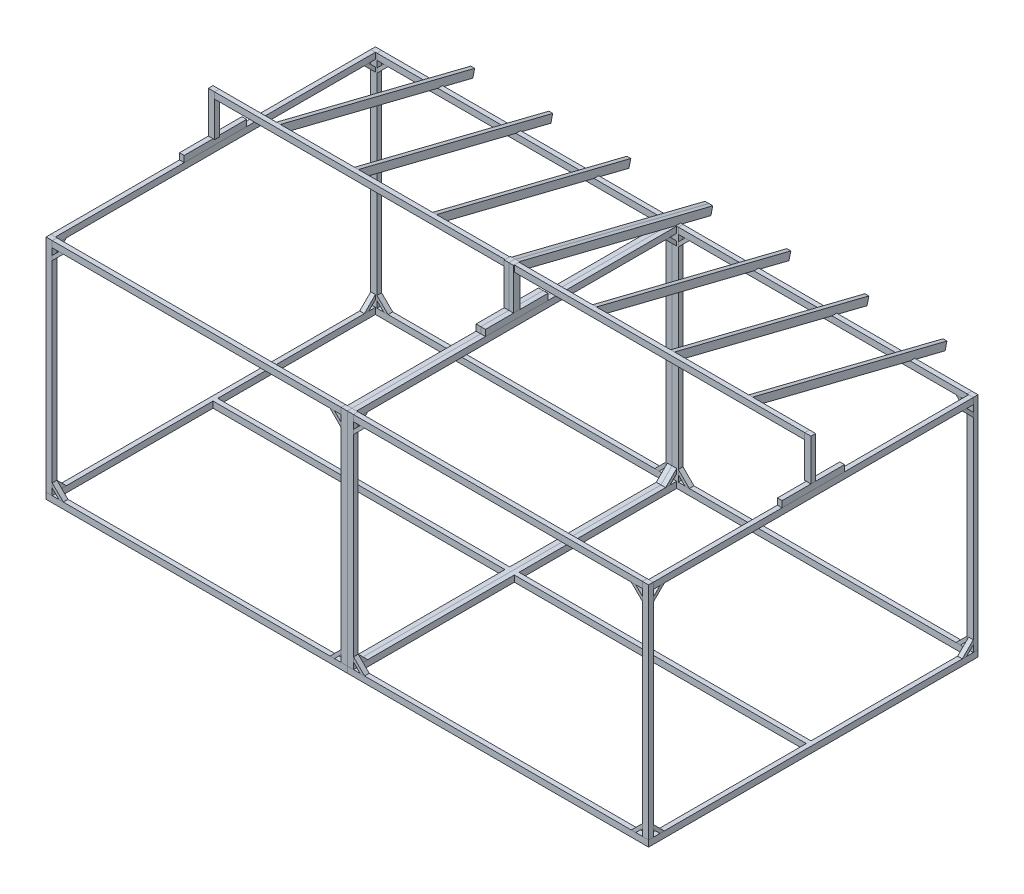
SolidWorks part; units mm, degrees
other "DetailItem8"
other "DetailItem9"
other "DetailItem10"
other "DetailItem11"
other "DetailItem12"
other "DetailItem13"
other "DetailItem14"
other "DetailItem15"
other "DetailItem16"
other "DetailItem17"
ref_plane "Front Plane" through (0, 0, 0) normal (0, 0, 1) x (1, 0, 0)
ref_plane "Top Plane" through (0, 0, 0) normal (0, 1, 0) x (1, 0, 0)
ref_plane "Right Plane" through (0, 0, 0) normal (1, 0, 0) x (0, 0, -1)
other "Configuration Table"
sketch "MetalBase" plane through (0, 0, 0) normal (0, 1, 0) x (1, 0, 0)
  line L0 (-60, -60) -> (7660, -60)
  line L1 (0, 0) -> (7600, 0)
  line L2 (0, 0) -> (0, 2020)
  line L3 (0, 4100) -> (7600, 4100)
  line L4 (7600, 0) -> (7600, 2020)
  line L5 (7660, -60) -> (7660, 4160)
  line L6 (-60, 4160) -> (7660, 4160)
  line L7 (-60, -60) -> (-60, 4160)
  line L8 (0, 2050) -> (7600, 2050) construction
  line L9 (0, 2020) -> (7600, 2020)
  line L10 (0, 2080) -> (7600, 2080)
  line L11 (0, 2080) -> (0, 4100)
  line L12 (7600, 2080) -> (7600, 4100)
  line L13 (0, 0) -> (0, 4100) construction
  line L15 (7600, 0) -> (7600, 4100) construction
  point P15 (7660, 2050)
  dimension "D1" = 4100
  dimension "D2" = 7600
  dimension "D6" = 4220
  dimension "D7" = 7720
  dimension "D3" = 60
  dimension "D4" = 30
  dimension "D5" = 30
sketch "InternalSpace" plane through (0, 0, 0) normal (0, 1, 0) x (1, 0, 0)
  line L26 (50, 50) -> (7550, 50)
  line L27 (7550, 50) -> (7550, 4050)
  line L28 (7550, 4050) -> (50, 4050)
  line L29 (50, 4050) -> (50, 50)
  line L30 (50, 50) -> (7550, 50)
  line L31 (7550, 50) -> (7550, 4050)
  line L32 (7550, 4050) -> (50, 4050)
  line L33 (50, 4050) -> (50, 50)
  dimension "D2" = 4000
  dimension "D3" = 7500
  dimension "D1" = 110
sketch "Furniture" [suppressed] plane through (0, 0, 0) normal (0, 1, 0) x (1, 0, 0)
  line L0 (6750, 2050) -> (6750, 4050)
  line L1 (2200, 2550) -> (1400, 2550)
  line L2 (2200, 2550) -> (2200, 4050)
  line L3 (2200, 4050) -> (1400, 4050)
  line L4 (1400, 2550) -> (1400, 4050)
  line L5 (1050, 50) -> (50, 50)
  line L6 (1050, 50) -> (1050, 2050)
  line L7 (1050, 2050) -> (50, 2050)
  line L8 (50, 50) -> (50, 2050)
  line L9 (6350, 2110) -> (7550, 2110)
  line L10 (2200, 4050) -> (2200, 150)
  line L11 (0, 0) -> (7600, 0) construction
  line L12 (6350, 50) -> (6350, 2110)
  line L13 (6470, 50) -> (6470, 1990)
  line L15 (2200, 2050) -> (7550, 2050) construction
  line L17 (1979.5569, 919.0285) -> (2200, 150)
  line L18 (6350, 150) -> (5722.0427, 459.305)
  line L19 (6710, 1120.0467) -> (7310, 1120.0467)
  line L24 (6710, 1120.0467) -> (6710, 1880.0467)
  line L25 (6710, 1880.0467) -> (7310, 1880.0467)
  line L26 (7310, 1120.0467) -> (7310, 1880.0467)
  line L27 (6350, 2110) -> (5750, 2110)
  line L28 (6350, 2110) -> (6350, 1510)
  line L29 (6350, 1510) -> (5750, 1510)
  line L30 (5750, 2110) -> (5750, 1510)
  line L31 (2320, 2050) -> (4320, 2050) construction
  line L32 (4320, 2050) -> (4320, 4050) construction
  line L33 (2200, 150) -> (2499.3532, 150) construction
  line L34 (2499.3532, 150) -> (2499.3532, 981.1813) construction
  line L35 (2499.3532, 981.1813) -> (2200, 981.1813) construction
  line L36 (2320, 4050) -> (2320, 150)
  line L37 (2200, 150) -> (2200, 50)
  line L38 (50, 50) -> (7550, 50) construction
  line L39 (2320, 150) -> (2320, 50)
  line L40 (7550, 4050) -> (50, 4050) construction
  line L41 (7550, 50) -> (7550, 4050) construction
  line L42 (50, 4050) -> (50, 50) construction
  line L43 (7550, 4050) -> (50, 4050) construction
  line L44 (7550, 50) -> (7550, 4050) construction
  line L45 (50, 50) -> (7550, 50) construction
  line L46 (50, 4050) -> (50, 50) construction
  line L47 (7010, 1120.0467) -> (7010, 1445.9123) construction
  line L48 (6470, 1990) -> (7550, 1990)
  line L49 (-60, -60) -> (-60, 4160) construction
  line L50 (7550, 809.8905) -> (7383.7397, 809.8905)
  line L51 (7550, 809.8905) -> (7550, 230.8186)
  line L52 (7550, 230.8186) -> (7383.7397, 230.8186)
  line L53 (7283.7397, 709.8905) -> (7283.7397, 330.8186)
  line L54 (7660, 4160) -> (-60, 4160) construction
  line L55 (-60, 4160) -> (-60, -60) construction
  line L56 (-60, -60) -> (7660, -60) construction
  line L57 (7660, -60) -> (7660, 4160) construction
  arc A1 (1979.5569, 919.0285) -> (1414.1883, 0) centre (2200, 150) ccw construction
  arc A2 (5722.0427, 459.305) -> (6350, 850) centre (6350, 150) cw construction
  arc A3 (7383.7397, 230.8186) -> (7283.7397, 330.8186) centre (7383.7397, 330.8186) cw
  arc A4 (7383.7397, 809.8905) -> (7283.7397, 709.8905) centre (7383.7397, 709.8905) ccw
  point P56 (7010, 1990)
  dimension "D13" = 600
  dimension "D21" = 100
  dimension "D1" = 1500
  dimension "D2" = 800
  dimension "D3" = 2000
  dimension "D4" = 1000
  dimension "D5" = 100
  dimension "D6" = 60
  dimension "D7" = 700
  dimension "D8" = 600
  dimension "D9" = 2260
  dimension "D10" = 800
  dimension "D11" = 100
  dimension "D12" = 760
  dimension "D14" = 2000
  dimension "D15" = 800
  dimension "D16" = 2000
  dimension "D17" = 600
  dimension "D18" = 60
  dimension "D19" = 4150
  dimension "D20" = 120
  dimension "D22" = 120
  dimension "D23" = 110
  dimension "D25" = 4220
  dimension "D26" = 1200
  dimension "D27" = 4030
  dimension "D24" = 110
sketch "Metal frame" plane through (0, 0, 0) normal (0, 1, 0) x (1, 0, 0)
  line L0 (0, 4100) -> (7600, 4100) construction
  line L1 (0, 4100) -> (7600, 4100)
  line L3 (0, 0) -> (0, 2020)
  line L4 (0, 0) -> (7600, 0) construction
  line L5 (0, 0) -> (7600, 0)
  line L7 (7600, 0) -> (7600, 2020)
  line L8 (-60, 4160) -> (7660, 4160)
  line L9 (7660, -60) -> (7660, 4160)
  line L10 (-60, -60) -> (7660, -60)
  line L11 (-60, -60) -> (-60, 4160)
  line L12 (0, 2050) -> (62.1159, 2050) construction
  line L13 (7600, 2080) -> (0, 2080)
  line L15 (7600, 2020) -> (0, 2020)
  line L17 (7600, 2080) -> (7600, 4100)
  line L18 (0, 2080) -> (0, 4100)
  line L19 (7600, 0) -> (7600, 4100) construction
  line L21 (0, 0) -> (0, 4100) construction
  point P14 (-60, 2050)
  dimension "D2" = 7720
  dimension "D3" = 4220
  dimension "D4" = 60
  dimension "D1" = 60
sketch "Walls bottom" plane through (0, 0, 0) normal (0, 1, 0) x (1, 0, 0)
  line L0 (-60, 4160) -> (7660, 4160) construction
  line L2 (-60, -60) -> (7660, -60) construction
  line L3 (7660, -60) -> (7660, 4160) construction
  line L4 (-60, -60) -> (-60, 4160) construction
  line L5 (-60, -60) -> (7660, -60)
  line L6 (7660, -60) -> (7660, 4160)
  line L7 (-60, 4160) -> (7660, 4160)
  line L8 (-60, -60) -> (-60, 4160)
  line L9 (40, 40) -> (40, 4060)
  line L10 (40, 4060) -> (7560, 4060)
  line L11 (7560, 40) -> (7560, 4060)
  line L12 (40, 40) -> (7560, 40)
  dimension "D2" = 4020
  dimension "D3" = 7520
  dimension "D4" = 7720
  dimension "D5" = 4220
  dimension "D1" = 100
sketch "Sketch15" [suppressed] plane through (0, 0, 0) normal (0, 1, 0) x (1, 0, 0)
  line L2 (7550, 50) -> (5502.4266, 50)
  line L3 (7550, 50) -> (7550, 1250)
  line L4 (7550, 1250) -> (5502.4266, 1250)
  line L5 (5502.4266, 50) -> (5502.4266, 1250)
  dimension "D1" = 1200
extrude "MetalFrame" add sketch "Metal frame" against normal blind 80 contours L11 L10 L9 L8 L15 L7 L5 L3 L13 L18 L1 L17 region at (3800, 0, -2050)
sketch "Sketch18" plane through (0, 0, 0) normal (0, 1, 0) x (1, 0, 0)
  line L0 (0, 0) -> (7600, 0) construction
  line L1 (3800, -1014.8769) -> (8467.9433, -1014.8769)
  line L2 (3800, -1014.8769) -> (3800, 5493.3133)
  line L3 (3800, 5493.3133) -> (8467.9433, 5493.3133)
  line L4 (8467.9433, -1014.8769) -> (8467.9433, 5493.3133)
  point P6 (3800, 0)
extrude "Cut-Extrude1" cut sketch "Sketch18" against normal through all
sketch "Sketch19" plane through (0, 0, 0) normal (0, 1, 0) x (1, 0, 0)
  line L0 (0, 0) -> (3800, 0) construction
  line L1 (3800, 4100) -> (3740, 4100)
  line L2 (3800, 4100) -> (3800, 0)
  line L3 (3800, 0) -> (3740, 0)
  line L4 (3740, 4100) -> (3740, 0)
  dimension "D1" = 60
extrude "Boss-Extrude1" add sketch "Sketch19" against normal blind 80
sketch "Roof" plane through (0, 0, 0) normal (1, 0, 0) x (0, 0, -1)
  line L0 (2050, 0) -> (2050, 3357.5) construction
  line L1 (4160, 0) -> (-60, 0) construction
  line L2 (4160, 0) -> (4160, 2830) construction
  line L3 (4160, 2830) -> (2050, 3357.5) construction
  line L4 (2050, 3357.5) -> (5424.8088, 3357.5) construction
  line L5 (4160, 2830) -> (4548.057, 2732.9857) construction
  line L6 (4160, 150) -> (-211.81, 150) construction
  line L7 (4160, 2830) -> (2960, 2830)
  line L8 (2960, 2830) -> (2960, 3130)
  line L9 (4160, 2750) -> (2401.0379, 2750) construction
  dimension "D2" = 1200
  dimension "D3" = 150
  dimension "D4" = 2174.9382
  dimension "D5" = 400
  dimension "D6" = 2574.9382
  dimension "D7" = 2830
  dimension "D8" = 300
  dimension "D9" = 3207.5
  dimension "D10" = 14.036
  dimension "D11" = 80
  dimension "D12" = 2600
sketch "Sketch23" plane through (-60, 0, 0) normal (1, 0, 0) x (0, 0, -1)
  line L0 (2050, 0) -> (2050, 3357.5) construction
  line L1 (4160, 0) -> (4100, 0)
  line L2 (4160, 0) -> (4160, 2830)
  line L3 (4160, 2830) -> (4100, 2830)
  line L4 (4100, 0) -> (4100, 2830)
  line L5 (0, 0) -> (0, 2830)
  line L6 (-60, 2830) -> (0, 2830)
  line L7 (-60, 0) -> (-60, 2830)
  line L8 (-60, 0) -> (0, 0)
  line L10 (0, 2830) -> (4100, 2830)
  line L11 (0, 2830) -> (0, 2750)
  line L12 (0, 2750) -> (4100, 2750)
  line L13 (4100, 2830) -> (4100, 2750)
  line M8 (-60, 0) -> (4160, 0)
  dimension "D1" = 60
  dimension "D2" = 80
extrude "Boss-Extrude5" add sketch "Sketch23" along normal blind 80 separate body contours L4 L3 L2 M8 | L7 L6 L5 M8 region at (-60, 1415, -4130) region at (-60, 1415, 30)
extrude "Boss-Extrude6" add sketch "Sketch23<3>" along normal blind 60 separate body contours L0 L12 L5 L10 | L12 L0 L10 L4 region at (-60, 2790, -1025) region at (-60, 2790, -3075)
sketch "Sketch23<3>" plane through (-60, 0, 0) normal (1, 0, 0) x (0, 0, -1) same geometry as "Sketch23"
extrude "Boss-Extrude7" add sketch "Sketch23<5>" against normal blind 80 from surface separate body contours L4 L3 L2 M8 | L7 L6 L5 M8 region at (-60, 1415, -4130) region at (-60, 1415, 30) starting at face at (3800, -40, -2050)
sketch "Sketch23<5>" plane through (-60, 0, 0) normal (1, 0, 0) x (0, 0, -1) same geometry as "Sketch23"
extrude "Boss-Extrude8" add sketch "Sketch23<6>" against normal blind 60 from surface separate body contours L12 L0 L10 L4 | L0 L12 L5 L10 region at (-60, 2790, -1025) region at (-60, 2790, -3075) starting at face at (3800, 1415, 30)
sketch "Sketch23<6>" plane through (-60, 0, 0) normal (1, 0, 0) x (0, 0, -1) same geometry as "Sketch23"
sketch "Sketch24" plane through (0, 2830, 0) normal (0, 1, 0) x (1, 0, 0)
  line L1 (20, 4160) -> (3720, 4160)
  line L2 (20, 4160) -> (20, 4100)
  line L3 (20, 4100) -> (3720, 4100)
  line L4 (3720, 4160) -> (3720, 4100)
  line L5 (20, 0) -> (3720, 0)
  line L6 (20, 0) -> (20, -60)
  line L7 (20, -60) -> (3720, -60)
  line L8 (3720, 0) -> (3720, -60)
extrude "Boss-Extrude9" add sketch "Sketch24" against normal blind 80 separate body
sketch "Sketch25" plane through (3800, 0, 0) normal (1, 0, 0) x (0, 0, -1)
  line L5 (2020, 2910) -> (2080, 2910)
  line L6 (2020, 2910) -> (2020, 3440)
  line L7 (2020, 3440) -> (2080, 3440)
  line L8 (2080, 2910) -> (2080, 3440)
  line L9 (2050, 0) -> (2050, 3357.5) construction
  line L10 (0, 2830) -> (4100, 2830) construction
  line L12 (1650, 2830) -> (2450, 2830)
  line L13 (1650, 2830) -> (1650, 2910)
  line L14 (1650, 2910) -> (2450, 2910)
  line L15 (2450, 2830) -> (2450, 2910)
  point P7 (2050, 3440)
  point P11 (2050, 2910)
  line M8 (4100, 2830) -> (0, 2830)
  dimension "D1" = 530
  dimension "D2" = 60
  dimension "D4" = 800
  dimension "D5" = 80
extrude "Boss-Extrude10" add sketch "Sketch25" along normal blind 80 from surface separate body contours L5 L8 L7 L6 region at (3800, 3175, -2050) starting at face at (-60, 2790, -2050)
extrude "Boss-Extrude13" add sketch "Sketch25<4>" against normal blind 60 from surface separate body contours L15 L14 L5 L13 M8 region at (3800, 2870, -2050) starting at face at (0, 2790, -2050)
sketch "Sketch25<4>" plane through (3800, 0, 0) normal (1, 0, 0) x (0, 0, -1) same geometry as "Sketch25"
extrude "Boss-Extrude20" add sketch "Sketch25<5>" against normal blind 60 separate body contours L15 L14 L5 L13 M8 region at (3800, 2870, -2050)
sketch "Sketch25<5>" plane through (3800, 0, 0) normal (1, 0, 0) x (0, 0, -1) same geometry as "Sketch25"
sketch "Sketch33" plane through (0, 2910, 0) normal (0, 1, 0) x (1, 0, 0)
  line L0 (3740, 1650) -> (3740, 2450) construction
  line L1 (3740, 2090) -> (3800, 2090)
  line L2 (3740, 2090) -> (3740, 2010)
  line L3 (3740, 2010) -> (3800, 2010)
  line L4 (3800, 2090) -> (3800, 2010)
  line L5 (3800, 1650) -> (3800, 2450) construction
  point P8 (3740, 2050)
  point P9 (3740, 2050)
  dimension "D1" = 80
extrude "Boss-Extrude21" add sketch "Sketch33" along normal up to surface (530 mm away) separate body up to face at (-20, 3440, -2050)
sketch "Sketch26" plane through (3800, 0, 0) normal (1, 0, 0) x (0, 0, -1)
  line L0 (4548.057, 2717.9857) -> (4160, 2815)
  line L1 (4548.057, 2717.9857) -> (4572.3106, 2815)
  line L3 (4572.3106, 2815) -> (2080, 3438.0776)
  line L4 (4100, 2815) -> (4100, 2830) construction
  line L5 (4100, 2830) -> (4160, 2830)
  line L6 (4160, 2830) -> (4160, 2815)
  line L7 (2080, 3335) -> (2080, 3438.0776)
  line L8 (4100, 2830) -> (2080, 3335)
  dimension "D1" = 100
extrude "Boss-Extrude12" add sketch "Sketch26" against normal blind 50 separate body
pattern_linear "LPattern1" count 4 spacing 1000 along (-1, 0, 0) of bodies 346
ref_plane "Plane1" through (1870, 0, 0) normal (-1, 0, 0) x (0, 0, 1)
sketch "Sketch27" plane through (3740, 0, 0) normal (-1, 0, 0) x (0, 0, 1)
  line L0 (-2020, 2910) -> (-2020, 3440) construction
  line L1 (-2080, 3440) -> (-2020, 3440)
  line L2 (-2080, 3440) -> (-2080, 3360)
  line L3 (-2080, 3360) -> (-2020, 3360)
  line L4 (-2020, 3440) -> (-2020, 3360)
  line L5 (-2050, 0) -> (-2050, 3357.5) construction
  point P4 (-2050, 3440)
  dimension "D1" = 80
  dimension "D2" = 60
extrude "Boss-Extrude22" add sketch "Sketch27" along normal up to surface (3720 mm away) separate body up to face at (20, 3175, -2050)
mirror "Mirror2" about plane through (3800, -80, 1014.8769) normal (-1, 0, 0) of bodies 336 338 340 342 335 337 339 341 330 412 411 349 348 347 346 410 350 351 354 352 353
sketch "Sketch28" plane through (0, 0, 60) normal (0, 0, 1) x (1, 0, 0)
  line L0 (20, 2665.1472) -> (104.8528, 2750)
  line L1 (20, 2750) -> (3720, 2750) construction
  line L2 (20, 0) -> (20, 2830) construction
  line L3 (20, 2608.5786) -> (161.4214, 2750)
  line L4 (20, 2665.1472) -> (20, 2750) construction
  line L5 (20, 2750) -> (104.8528, 2750) construction
  line L6 (3720, 2750) -> (20, 0) construction
  line L7 (20, 2750) -> (3720, 0) construction
  line L8 (104.8528, 2750) -> (161.4214, 2750)
  line L9 (20, 2665.1472) -> (20, 2608.5786)
  line L10 (1870, 1375) -> (1870, 2476.0047) construction
  line L11 (1870, 1375) -> (689.8346, 1375) construction
  line L12 (20, 0) -> (104.8528, 0) construction
  line L13 (20, 84.8528) -> (20, 0) construction
  line L14 (20, 84.8528) -> (20, 141.4214)
  line L15 (104.8528, 0) -> (161.4214, 0)
  line L16 (20, 141.4214) -> (161.4214, 0)
  line L17 (20, 84.8528) -> (104.8528, 0)
  line L18 (3720, 84.8528) -> (3720, 0) construction
  line L19 (3720, 0) -> (3635.1472, 0) construction
  line L20 (3720, 2750) -> (3635.1472, 2750) construction
  line L21 (3720, 2665.1472) -> (3720, 2750) construction
  line L22 (3720, 84.8528) -> (3635.1472, 0)
  line L23 (3720, 141.4214) -> (3578.5786, 0)
  line L24 (3635.1472, 0) -> (3578.5786, 0)
  line L25 (3720, 84.8528) -> (3720, 141.4214)
  line L26 (3720, 2665.1472) -> (3720, 2608.5786)
  line L27 (3635.1472, 2750) -> (3578.5786, 2750)
  line L28 (3720, 2608.5786) -> (3578.5786, 2750)
  line L29 (3720, 2665.1472) -> (3635.1472, 2750)
  line L30 (3800, -80) -> (3800, -237.922) construction
  line L31 (3880, 2665.1472) -> (3880, 2750) construction
  line L32 (3880, 2750) -> (3964.8528, 2750) construction
  line L33 (3880, 0) -> (3964.8528, 0) construction
  line L34 (3880, 84.8528) -> (3880, 0) construction
  line L35 (7580, 84.8528) -> (7580, 0) construction
  line L36 (7580, 0) -> (7495.1472, 0) construction
  line L37 (5730, 1375) -> (6910.1654, 1375) construction
  line L38 (5730, 1375) -> (5730, 2476.0047) construction
  line L39 (7580, 2750) -> (3880, 0) construction
  line L40 (3880, 2750) -> (7580, 0) construction
  line L41 (7580, 2750) -> (7495.1472, 2750) construction
  line L42 (7580, 2665.1472) -> (7580, 2750) construction
  line L43 (3880, 2665.1472) -> (3964.8528, 2750)
  line L44 (3880, 2608.5786) -> (4021.4214, 2750)
  line L45 (3964.8528, 2750) -> (4021.4214, 2750)
  line L46 (3880, 2665.1472) -> (3880, 2608.5786)
  line L47 (3880, 84.8528) -> (3880, 141.4214)
  line L48 (3964.8528, 0) -> (4021.4214, 0)
  line L49 (3880, 141.4214) -> (4021.4214, 0)
  line L50 (3880, 84.8528) -> (3964.8528, 0)
  line L51 (7580, 84.8528) -> (7495.1472, 0)
  line L52 (7580, 141.4214) -> (7438.5786, 0)
  line L53 (7495.1472, 0) -> (7438.5786, 0)
  line L54 (7580, 84.8528) -> (7580, 141.4214)
  line L55 (7580, 2665.1472) -> (7580, 2608.5786)
  line L56 (7495.1472, 2750) -> (7438.5786, 2750)
  line L57 (7580, 2608.5786) -> (7438.5786, 2750)
  line L58 (7580, 2665.1472) -> (7495.1472, 2750)
  point P14 (1870, 1375)
  point P58 (5730, 1375)
  dimension "D1" = 40
  dimension "D2" = 200
extrude "Boss-Extrude15" add sketch "Sketch28" against normal blind 60 separate body
ref_plane "Plane2" through (0, 0, -2050) normal (0, 0, 1) x (1, 0, 0)
mirror "Mirror5" about plane through (0, 0, -2050) normal (0, 0, 1) of bodies 379 382 378 377 380 381 384 383
sketch "Sketch29" plane through (-60, 0, 0) normal (-1, 0, 0) x (0, 0, 1)
  line L0 (-141.4214, 2750) -> (0, 2608.5786)
  line L1 (0, 2750) -> (-4100, 2750) construction
  line L2 (0, 0) -> (0, 2830) construction
  line L3 (0, 2608.5786) -> (0, 2665.1472)
  line L4 (0, 2665.1472) -> (-84.8528, 2750)
  line L5 (-84.8528, 2750) -> (-141.4214, 2750)
  line L6 (-141.4214, 2750) -> (0, 2750) construction
  line L7 (0, 2750) -> (0, 2608.5786) construction
  line L8 (-4100, 2750) -> (0, 0) construction
  line L9 (0, 2750) -> (-4100, 0) construction
  line L10 (-2050, 1375) -> (-2050, 2472.0101) construction
  line L11 (-2050, 0) -> (-2050, 3357.5) construction
  line L12 (-2050, 1375) -> (-3378.9698, 1375) construction
  line L13 (-4100, 2750) -> (-4100, 2608.5786) construction
  line L14 (-3958.5786, 2750) -> (-4100, 2750) construction
  line L15 (-4015.1472, 2750) -> (-3958.5786, 2750)
  line L16 (-4100, 2665.1472) -> (-4015.1472, 2750)
  line L17 (-4100, 2608.5786) -> (-4100, 2665.1472)
  line L18 (-3958.5786, 2750) -> (-4100, 2608.5786)
  line L19 (-3958.5786, 0) -> (-4100, 0) construction
  line L20 (-4100, 0) -> (-4100, 141.4214) construction
  line L21 (0, 0) -> (0, 141.4214) construction
  line L22 (-141.4214, 0) -> (0, 0) construction
  line L23 (-3958.5786, 0) -> (-4100, 141.4214)
  line L24 (-4100, 141.4214) -> (-4100, 84.8528)
  line L25 (-4100, 84.8528) -> (-4015.1472, 0)
  line L26 (-4015.1472, 0) -> (-3958.5786, 0)
  line L27 (-84.8528, 0) -> (-141.4214, 0)
  line L28 (0, 84.8528) -> (-84.8528, 0)
  line L29 (0, 141.4214) -> (0, 84.8528)
  line L30 (-141.4214, 0) -> (0, 141.4214)
  dimension "D1" = 200
  dimension "D2" = 40
extrude "Boss-Extrude16" add sketch "Sketch29" against normal blind 60 separate body
extrude "Boss-Extrude17" add sketch "Sketch29<2>" against normal blind 60 from surface separate body starting at face at (3740, 2790, -2050)
sketch "Sketch29<2>" plane through (-60, 0, 0) normal (-1, 0, 0) x (0, 0, 1) same geometry as "Sketch29"
extrude "Boss-Extrude18" add sketch "Sketch29<4>" against normal blind 60 from surface separate body starting at face at (3800, 2790, -2050)
sketch "Sketch29<4>" plane through (-60, 0, 0) normal (-1, 0, 0) x (0, 0, 1) same geometry as "Sketch29"
extrude "Boss-Extrude19" add sketch "Sketch29<5>" against normal blind 60 from surface separate body starting at face at (7600, 2790, -2050)
sketch "Sketch29<5>" plane through (-60, 0, 0) normal (-1, 0, 0) x (0, 0, 1) same geometry as "Sketch29"
